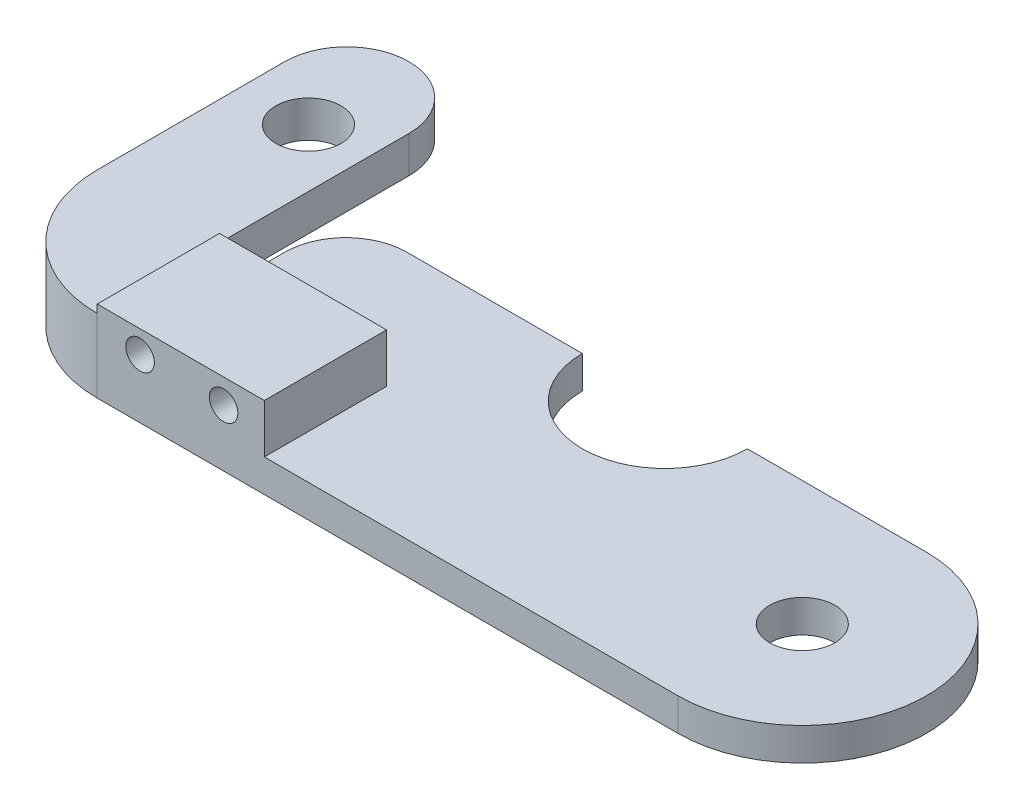
SolidWorks part; units mm, degrees
ref_plane "Front Plane" through (0, 0, 0) normal (0, 0, 1) x (1, 0, 0)
ref_plane "Top Plane" through (0, 0, 0) normal (0, 1, 0) x (1, 0, 0)
ref_plane "Right Plane" through (0, 0, 0) normal (1, 0, 0) x (0, 0, -1)
sketch "Sketch1" plane through (0, 0, 0) normal (0, 1, 0) x (1, 0, 0)
  line L0 (-13.6869, -1.9274) -> (14.8131, -1.9274)
  line L1 (14.8131, -1.9274) -> (14.8131, 4.1726) construction
  line L2 (14.8131, 10.2726) -> (6.0201, 10.2726)
  line L3 (-13.6869, 7.2726) -> (-13.6869, 4.1726)
  line L4 (-2.0799, 10.2726) -> (-10.6869, 10.2726)
  line L5 (-13.6869, 4.1726) -> (-19.7869, 4.1726) construction
  line L6 (-13.6869, 4.1726) -> (-13.6869, -1.9274)
  arc A0 (14.8131, -1.9274) -> (14.8131, 10.2726) centre (14.8131, 4.1726) ccw
  circle A1 centre (14.8131, 4.1726) radius 1.6
  arc A2 (-10.6869, 10.2726) -> (-13.6869, 7.2726) centre (-10.6869, 7.2726) ccw
  arc A3 (-2.0799, 10.2726) -> (6.0201, 10.2726) centre (1.9701, 10.2726) ccw
  arc A4 (-19.7869, 4.1726) -> (-13.6869, -1.9274) centre (-13.6869, 4.1726) ccw construction
  dimension "D3" = 3.2
  dimension "D4" = 6
  dimension "D5" = 8.1
  dimension "D1" = 28.5
  dimension "D2" = 6.1
  dimension "D6" = 6.1
  dimension "D7" = 11.607
extrude "Boss-Extrude1" add sketch "Sketch1" along normal blind 1.6
sketch "Sketch2" plane through (0, 1.6, 0) normal (0, 1, 0) x (1, 0, 0)
  line L1 (-13.6869, -1.9274) -> (-5.4869, -1.9274)
  line L2 (-13.6869, -1.9274) -> (-13.6869, 4.0726)
  line L3 (-13.6869, 4.0726) -> (-5.4869, 4.0726)
  line L4 (-5.4869, -1.9274) -> (-5.4869, 4.0726)
  dimension "D1" = 8.2
  dimension "D2" = 6
extrude "Boss-Extrude2" add sketch "Sketch2" along normal blind 2.4
sketch "Sketch3" plane through (0, 0, 1.9274) normal (0, 0, 1) x (1, 0, 0)
  line L0 (-5.4869, 4) -> (-5.4869, 1.6) construction
  line L1 (-13.6869, 4) -> (-5.4869, 4) construction
  circle A0 centre (-11.5857, 2.9) radius 0.7
  circle A1 centre (-7.4869, 2.8) radius 0.7
  dimension "D1" = 1.4
  dimension "D2" = 1.4
  dimension "D3" = 2
  dimension "D4" = 4.1
  dimension "D5" = 1.2
extrude "Cut-Extrude1" cut sketch "Sketch3" against normal up to surface (6 mm away) up to face at (-9.5869, 2.8, -4.0726)
ref_plane "Plane1" through (0, 1.8, 0) normal (0, 1, 0) x (1, 0, 0)
sketch "Sketch4" plane through (0, 0, 0) normal (0, -1, 0) x (1, 0, 0)
  line L0 (-13.6869, 1.9274) -> (-13.6869, -4.1726)
  line L2 (-13.6869, -4.1726) -> (-19.7869, -4.1726)
  arc A0 (-13.6869, 1.9274) -> (-19.7869, -4.1726) centre (-13.6869, -4.1726) ccw
  dimension "D1" = 6.1
extrude "Boss-Extrude3" add sketch "Sketch4" against normal blind 3.6 separate body
sketch "Sketch5" plane through (0, 0, -4.1726) normal (0, 0, -1) x (-1, 0, 0)
  line L0 (19.7869, 3.6) -> (19.7869, 0) construction
  line L1 (13.6869, 3.6) -> (19.7869, 3.6)
  line L2 (13.6869, 3.6) -> (13.6869, 1.8)
  line L3 (13.6869, 1.8) -> (19.7869, 1.8)
  line L4 (19.7869, 3.6) -> (19.7869, 1.8)
  line L5 (2.0799, 1.6) -> (10.6869, 1.6) construction
  dimension "D1" = 0.2
extrude "Boss-Extrude4" add sketch "Sketch5" along normal blind 9.2
sketch "Sketch6" plane through (0, 3.6, 0) normal (0, 1, 0) x (1, 0, 0)
  line L0 (-19.7869, 13.3726) -> (-13.6869, 13.3726) construction
  line L1 (-19.7869, 13.3726) -> (-13.6869, 13.3726)
  arc A0 (-13.6869, 13.3726) -> (-19.7869, 13.3726) centre (-16.7369, 13.3726) ccw
extrude "Boss-Extrude5" add sketch "Sketch6" against normal up to surface (1.8 mm away) up to face at (-16.7369, 1.8, -8.7726)
sketch "Sketch7" plane through (0, 3.6, 0) normal (0, 1, 0) x (1, 0, 0)
  circle A0 centre (-16.53, 11.2801) radius 1.6
  circle A1 centre (-16.53, 11.2801) radius 1.6 construction
  dimension "D2" = 3.2
  dimension "D1" = 0
extrude "Cut-Extrude2" cut sketch "Sketch7" against normal up to surface (1.8 mm away) up to face at (-16.7369, 1.8, -9.5351)
